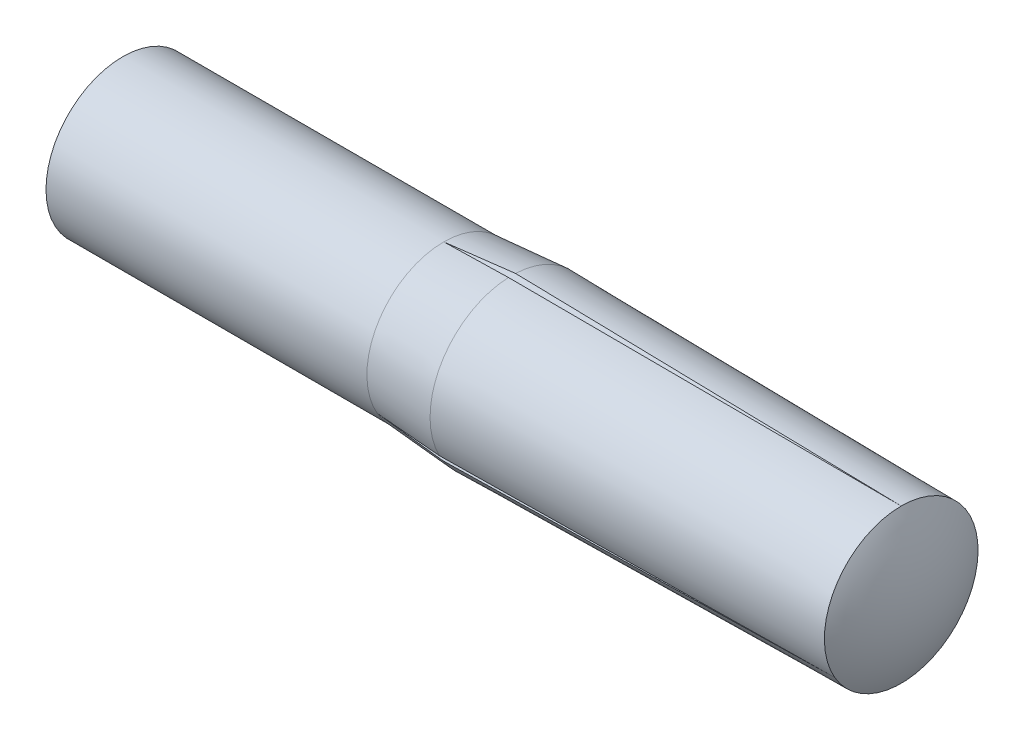
SolidWorks part; units mm, degrees
ref_plane "Plane1" through (0, 0, 0) normal (0, 0, 1) x (1, 0, 0)
ref_plane "Plane2" through (0, 0, 0) normal (0, 1, 0) x (1, 0, 0)
ref_plane "Plane3" through (0, 0, 0) normal (1, 0, 0) x (0, 0, -1)
sketch "Sketch1" plane through (0, 0, 0) normal (0, 0, 1) x (1, 0, 0)
  line L0 (0, 0) -> (24.8397, 0) construction
  line L1 (0.88, 0) -> (-0.88, 0) construction
  line L2 (0.2, 0.75) -> (3.3333, 0.75)
  line L4 (3.3333, 0.75) -> (4, 0.8)
  line L5 (4, 0.8) -> (7.8, 0.75)
  line L6 (0, 0) -> (8, 0)
  line L7 (8, 0) -> (8, -1.4225) construction
  arc A0 (0, 0) -> (0.2, 0.75) centre (1.5063, 0) cw
  arc A1 (7.8, 0.75) -> (8, 0) centre (6.4937, 0) cw
  dimension "c2" = 0.2
  dimension "d" = 1.5
  dimension "D1" = 0.2
  dimension "l" = 8
  dimension "D3" = 4
  dimension "D2" = 1.6
  dimension "D5" = 1.5
  dimension "D4" = 0.6667
revolve "Revolve2" add sketch "Sketch1" angle 360 about L0
sketch "Sketch2" plane through (0, 0, 0) normal (1, 0, 0) x (0, 0, -1)
  line L0 (0, 0.75) -> (-0.07, 0.85)
  line L1 (0, 0.8796) -> (0, -0.8796) construction
  line L2 (-0.07, 0.85) -> (0.07, 0.85)
  line L3 (0.07, 0.85) -> (0, 0.75)
  line L4 (0, 0.85) -> (0, 0.75) construction
  circle A0 centre (0, 0) radius 0.75 construction
  dimension "D1" = 0.1
  dimension "D2" = 70
extrude "Cut-Extrude2" cut sketch "Sketch2" along normal through all
pattern_circular "CirPattern2" count 3 over 360 about axis through (0, 0, 0) along (1, 0, 0) of "Cut-Extrude2"
equation "\"D1@Sketch1\" = \"c2@Sketch1\""
equation "\"D3@Sketch1\" = \"l@Sketch1\" / 2"
equation "\"D5@Sketch1\" = \"d@Sketch1\""
equation "\"D1@Sketch2\" = \"D2@Sketch1\" - \"d@Sketch1\""
equation "\"D4@Sketch1\" = \"D3@Sketch1\" / 6"
